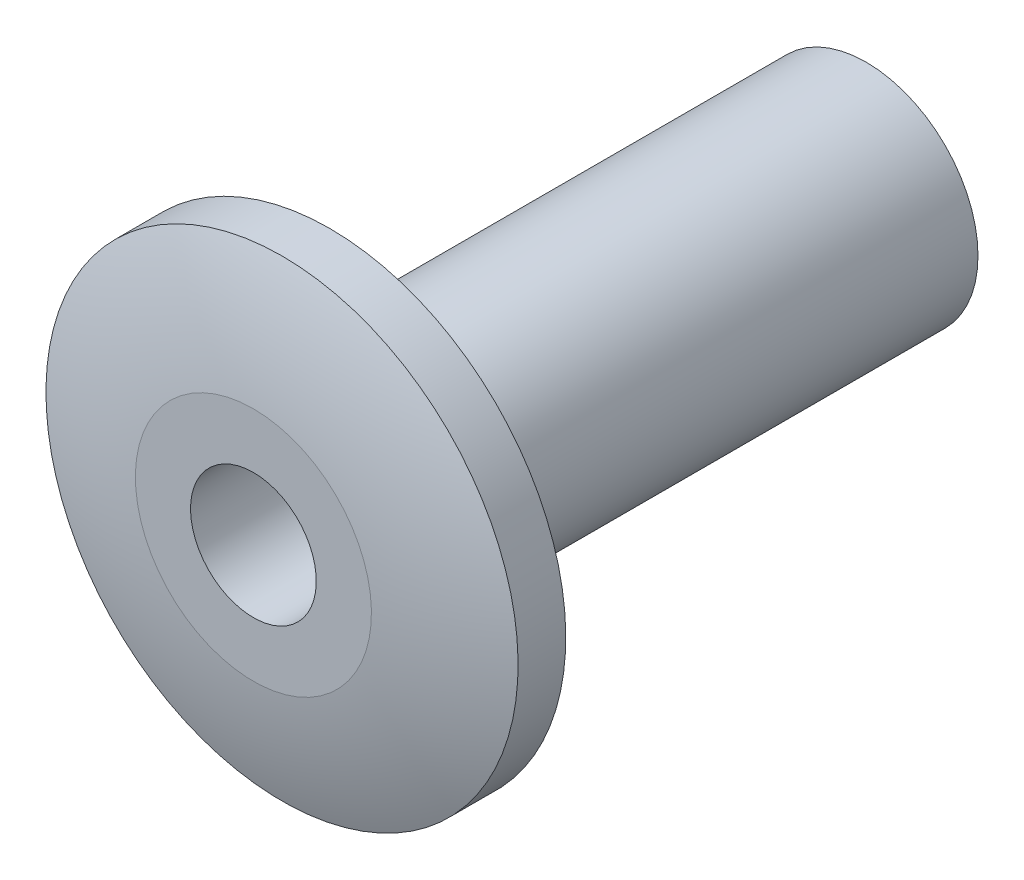
SolidWorks part; units mm, degrees
material "3003-H14"
ref_plane "Front" through (0, 0, 0) normal (0, 0, 1) x (1, 0, 0)
ref_plane "Top" through (0, 0, 0) normal (0, 1, 0) x (1, 0, 0)
ref_plane "Right" through (0, 0, 0) normal (1, 0, 0) x (0, 0, -1)
sketch "Sketch1" plane through (0, 0, 0) normal (1, 0, 0) x (0, 0, -1)
  line L0 (-9.3853, 0) -> (-0.8128, 0) construction
  line L1 (-0.8128, 0) -> (0, 0) construction
  line L2 (0, 0) -> (5.715, 0) construction
  line L3 (5.715, 0) -> (6.9342, 0) construction
  line L8 (0, 2.5146) -> (0, -2.5146) construction
  line L9 (5.715, 1.1906) -> (5.715, -1.1906) construction
  dimension "Length" = 5.715
  dimension "Head Height" = 0.8128
  dimension "D5" = 1.2192
  dimension "D9" = 8.5725
  dimension "Diameter" = 2.3813
  dimension "Head Diameter" = 5.0292
sketch "Sketch2" plane through (0, 0, 0) normal (1, 0, 0) x (0, 0, -1)
  line L0 (-9.3853, 0.5953) -> (-9.3853, 0) construction
  line L1 (-9.3853, 0.5953) -> (0, 0.5953) construction
  line L2 (0, 2.5146) -> (0, -2.5146) construction
  line L3 (0, 0) -> (0, 2.5146) construction
  line L4 (-0.8128, 0) -> (-0.8128, -1.8472) construction
  line L5 (5.715, 1.1906) -> (0, 1.1906)
  line L6 (5.715, 1.1906) -> (5.715, 0) construction
  line L7 (6.9342, 0) -> (6.9342, 1.1906) construction
  line L8 (5.715, 1.1906) -> (5.715, 0)
  line L9 (6.9342, 1.1906) -> (5.715, 1.1906) construction
  line L10 (-0.8128, 0.6697) -> (-0.8128, 1.2573)
  line L11 (5.715, 0) -> (6.9342, 0) construction
  line L12 (5.715, 0) -> (0.5715, 0)
  line L13 (-0.8128, 0.5953) -> (-0.8128, 0) construction
  line L14 (5.715, 1.1906) -> (5.715, 0) construction
  line L15 (5.715, 1.1906) -> (5.715, 0) construction
  line L16 (5.715, 0) -> (5.715, 1.1906) construction
  line L17 (5.715, 1.1906) -> (5.715, 0) construction
  line L18 (5.715, 0) -> (5.715, 1.1906) construction
  line L19 (0, 1.1906) -> (0, 2.5146)
  line L20 (-0.8128, 0.6697) -> (0, 0.6697)
  line L21 (-9.3853, 0.6697) -> (0, 0.6697) construction
  line L22 (0, 2.5146) -> (-0.508, 2.5146)
  line L23 (0, 0.6697) -> (0.5715, 0.6697)
  line L24 (0.5715, 0.6697) -> (0.5715, 0)
  arc A0 (6.9342, 0) -> (5.715, 0.9525) centre (5.9525, 0) ccw construction
  arc A2 (-0.508, 2.5146) -> (-0.8128, 1.2573) centre (4.6635, 0.5953) ccw
  dimension "D3" = 0.508
  dimension "D1" = 0.5953
  dimension "D2" = 0.5715
  dimension "D5" = 0.9525
  dimension "D6" = 1.2573
  dimension "D4" = 0.0744
revolve "Revolve1" add sketch "Sketch2" angle 360 about L12
sketch "Sketch7" plane through (0, 0, 0) normal (1, 0, 0) x (0, 0, -1)
  line L0 (-8.8206, 0.5953) -> (0.5715, 0.5953)
  line L1 (0.5715, 0.6697) -> (0.5715, 0) construction
  line L2 (0.5715, 0.5953) -> (0.5715, 0)
  line L3 (0.5715, 0) -> (-9.3853, 0)
  line L5 (-9.2923, 0.1995) -> (-8.8206, 0.5953)
  arc A0 (-9.3853, 0) -> (-9.2923, 0.1995) centre (-9.1249, 0) cw
  dimension "D1" = 0.2604
  dimension "D2" = 40
revolve "Revolve2" [suppressed] add sketch "Sketch7" angle 360 about L0
sketch "Sketch8" plane through (0, 0, 0) normal (1, 0, 0) x (0, 0, -1)
  line L1 (5.715, 0.9525) -> (5.715, 0)
  line L2 (5.715, 0) -> (6.9342, 0) construction
  line L3 (6.9342, 0) -> (5.9525, 0) construction
  line L4 (6.6888, 0) -> (5.715, 0)
  line L5 (5.715, 0.9525) -> (6.0713, 0.9525) construction
  arc A0 (6.9342, 0) -> (5.715, 0.9525) centre (5.9525, 0) ccw construction
  arc A1 (6.0713, 0.9745) -> (5.715, 0.9525) centre (5.9525, 0) ccw
  arc A2 (6.0713, 0.9745) -> (6.6888, 0) centre (5.6111, 0) cw
  circle A3 centre (5.9525, 0) radius 0.9817 construction
  point P7 (6.6888, 0)
  point P8 (6.4434, 0)
  point P9 (6.1979, 0)
  point P12 (5.8338, 0.9525)
  point P13 (5.9525, 0.9525)
revolve "Revolve3" [suppressed] add sketch "Sketch8" angle 360 about L3
sketch "Sketch3" [suppressed] plane through (0, 0, 0) normal (0, 1, 0) x (1, 0, 0)
  line L0 (-0.7985, -7.6465) -> (-0.1657, -9.3853)
  line L1 (-0.1657, -9.3853) -> (0.1657, -9.3853)
  line L3 (0, -9.3853) -> (0, -9.8933) construction
  line L4 (0.1995, -9.2923) -> (-0.1995, -9.2923) construction
  line L5 (-0.7985, -7.6465) -> (-0.7985, -9.8933)
  line L6 (-0.7985, -9.8933) -> (0.7985, -9.8933)
  line L7 (0.7985, -9.8933) -> (0.7985, -7.6465)
  line L8 (-0.5953, 0.5715) -> (-0.5953, -8.8206) construction
  line L9 (0, -9.3853) -> (0, -0.8128) construction
  line L10 (0.1657, -9.3853) -> (0.7985, -7.6465)
  line L11 (-0.5953, -8.8206) -> (-0.1995, -9.2923) construction
  arc A0 (-0.1995, -9.2923) -> (0.1995, -9.2923) centre (0, -9.1249) ccw construction
  point P11 (-0.1995, -9.2923)
  point P25 (0, -9.3853)
  dimension "D1" = 40
  dimension "D2" = 0.2032
  dimension "D3" = 0.508
extrude "Cut-Extrude1" [suppressed] cut sketch "Sketch3" against normal through all both and the other way through all
pattern_circular "CirPattern1" [suppressed] count 2 every 90 about axis through (0, 0, 9.3853) along (0, 0, -1) of bodies 111
sketch "Sketch9" [suppressed] plane through (0, 0, 0) normal (0, 1, 0) x (1, 0, 0)
  line L0 (0, -9.3853) -> (0, 19.9517) construction
  line L1 (0, 5.715) -> (0, 6.9342) construction
  line L2 (2.5146, 0) -> (-2.5146, 0) construction
  line L3 (1.5316, 0) -> (1.6066, 0)
  line L4 (1.5316, 0) -> (1.5316, 0.0254)
  line L5 (1.5316, 0.0254) -> (1.6066, 0.0254)
  line L6 (1.6066, 0) -> (1.6066, 0.0254)
  line L8 (1.739, 0) -> (1.8139, 0)
  line L9 (1.739, 0) -> (1.739, 0.0254)
  line L10 (1.739, 0.0254) -> (1.8139, 0.0254)
  line L11 (1.8139, 0) -> (1.8139, 0.0254)
  line L12 (1.9238, 0) -> (1.9987, 0)
  line L13 (1.9238, 0) -> (1.9238, 0.0254)
  line L14 (1.9238, 0.0254) -> (1.9987, 0.0254)
  line L15 (1.9987, 0) -> (1.9987, 0.0254)
  line L16 (2.1911, 0) -> (2.266, 0)
  line L17 (2.1911, 0) -> (2.1911, 0.0254)
  line L18 (2.1911, 0.0254) -> (2.266, 0.0254)
  line L19 (2.266, 0) -> (2.266, 0.0254)
  line L20 (1.4342, 0) -> (1.3592, 0)
  line L21 (1.4342, 0) -> (1.4342, 0.0254)
  line L22 (1.4342, 0.0254) -> (1.3592, 0.0254)
  line L23 (1.3592, 0) -> (1.3592, 0.0254)
  point P24 (2.2286, 0.0254)
  point P25 (1.9613, 0.0254)
  point P26 (1.7764, 0.0254)
  point P27 (1.5691, 0.0254)
  point P32 (1.3967, 0.0254)
  dimension "D1" = 0.0749
  dimension "D2" = 0.0254
  dimension "D3" = 4.4571
  dimension "D4" = 3.9226
  dimension "D5" = 3.5528
  dimension "D6" = 3.1382
  dimension "D7" = 2.7934
revolve "Revolve4" [suppressed] add sketch "Sketch9" angle 360 about L0
equation "\"D5@Sketch1\" = \"Head Height@Sketch1\" * 1.5"
equation "\"D9@Sketch1\" = \"Length@Sketch1\" * 1.5"
equation "\"D1@Sketch2\"=\"Diameter@Sketch1\"/4"
equation "\"D4@Sketch2\"=\"D1@Sketch2\"/8"
equation "\"D2@Sketch2\"=\"Length@Sketch1\"/10"
equation "\"D5@Sketch2\"=\"Diameter@Sketch1\"*.8/2"
equation "\"D1@Sketch7\"=(\"D1@Sketch2\"-\"D4@Sketch2\")*2*.25"
equation "\"D6@Sketch2\"=\"Head Diameter@Sketch1\"/2*.5"
equation "\"D7@Sketch9\"=.15566*(\"Head Diameter@Sketch1\"-\"Diameter@Sketch1\")+\"Diameter@Sketch1\""
equation "\"D3@Sketch9\"=.7839623*(\"Head Diameter@Sketch1\"-\"Diameter@Sketch1\")+\"Diameter@Sketch1\""
equation "\"D1@Sketch9\"=.028302*(\"Head Diameter@Sketch1\"-\"Diameter@Sketch1\")"
equation "\"D6@Sketch9\"=.285849*(\"Head Diameter@Sketch1\"-\"Diameter@Sketch1\")+\"Diameter@Sketch1\""
equation "\"D5@Sketch9\"=.4424528*(\"Head Diameter@Sketch1\"-\"Diameter@Sketch1\")+\"Diameter@Sketch1\""
equation "\"D4@Sketch9\"=.582075*(\"Head Diameter@Sketch1\"-\"Diameter@Sketch1\")+\"Diameter@Sketch1\""
